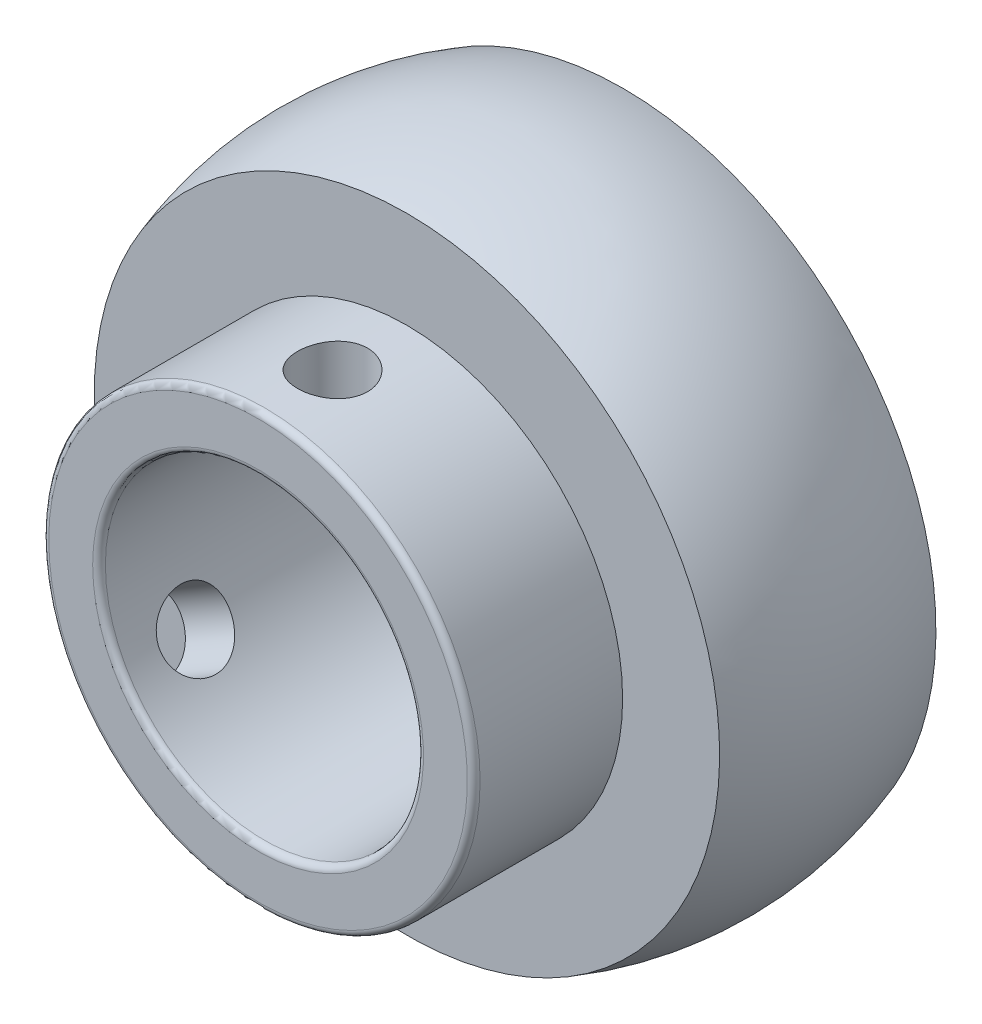
SolidWorks part; units mm, degrees
material "AISI 1020"
ref_plane "Спереди" through (0, 0, 0) normal (0, 0, 1) x (1, 0, 0)
ref_plane "Сверху" through (0, 0, 0) normal (0, 1, 0) x (1, 0, 0)
ref_plane "Справа" through (0, 0, 0) normal (1, 0, 0) x (0, 0, -1)
sketch "Эскиз1" plane through (0, 0, 0) normal (1, 0, 0) x (0, 0, -1)
  line L0 (-1108.8091, 0) -> (54331.6441, 0) construction
  line L1 (17, 16.95) -> (22.5, 16.95)
  line L2 (-11.7, 16.95) -> (0, 16.95)
  line L3 (-11.7, 16.95) -> (-11.7, 12.5)
  line L4 (-11.7, 12.5) -> (22.5, 12.5)
  line L5 (22.5, 16.95) -> (22.5, 12.5)
  line L7 (0, 16.95) -> (0, 24.5713)
  line L9 (17, 16.95) -> (17, 24.5713)
  arc A0 (0, 24.5713) -> (17, 24.5713) centre (8.5, 0) cw
  dimension "D6" = 52
  dimension "D1" = 25
  dimension "D2" = 33.9
  dimension "D3" = 17
  dimension "D4" = 34.2
  dimension "D5" = 11.7
revolve "Повернуть1" add sketch "Эскиз1" angle 360 about L0
sketch "Эскиз2" plane through (0, 0, 0) normal (0, 1, 0) x (1, 0, 0)
  line L0 (-16.95, -5.85) -> (16.95, -5.85) construction
  line L1 (-16.95, 0) -> (-16.95, -11.7) construction
  line L2 (16.95, -11.7) -> (16.95, 0) construction
  circle A0 centre (0, -5.85) radius 2.75
  dimension "D1" = 5.5
extrude "Вырез-Вытянуть1" cut sketch "Эскиз2" along normal through all
ref_axis "Ось1" through (0, 0, 50) along (0, 0, -1)
ref_plane "Плоскость1" through (0, 0, 0) normal (0.866, 0.5, 0) x (0, 0, -1)
sketch "Эскиз3" plane through (0, 0, 0) normal (0.866, 0.5, 0) x (0, 0, -1)
  circle A0 centre (-5.85, 0) radius 2.75
  dimension "D1" = 5.5
extrude "Вырез-Вытянуть2" cut sketch "Эскиз3" against normal through all
fillet "Скругление1" radius 0.5 4 edges at (12.5, 0, -22.5) (16.95, 0, -22.5) (12.5, 0, 11.7) (16.95, 0, 11.7)
